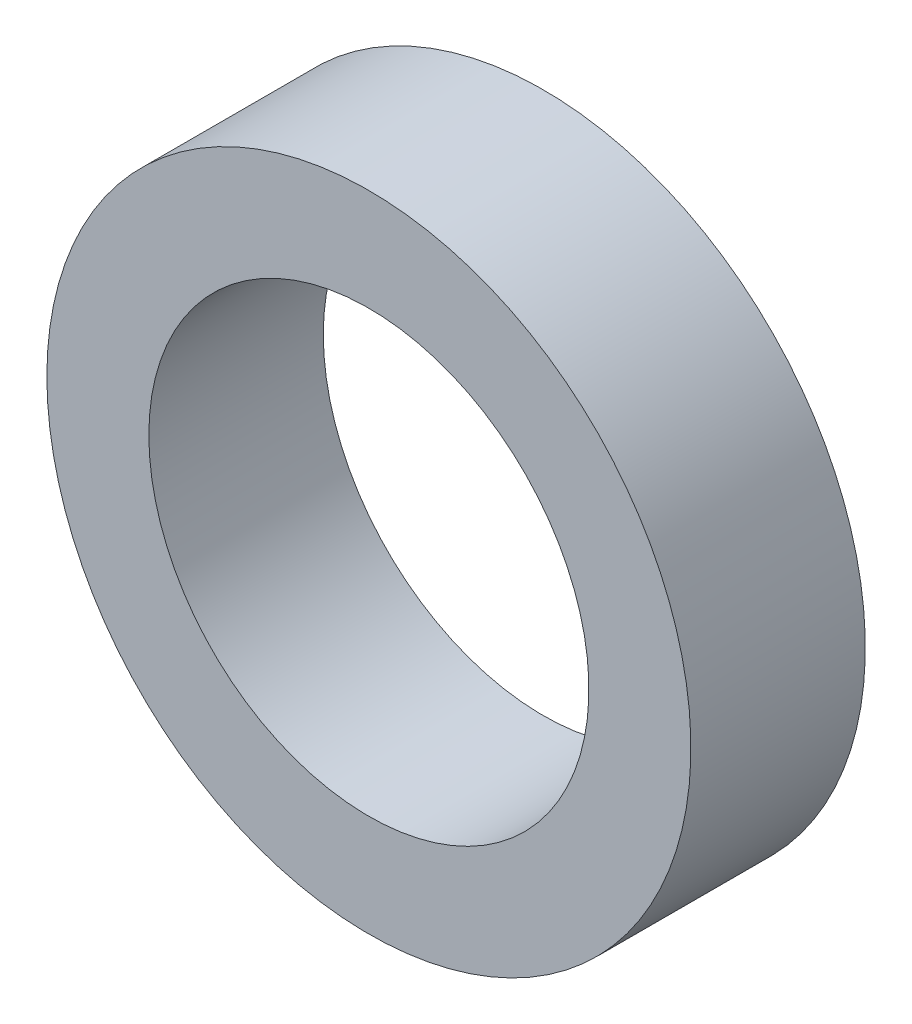
SolidWorks part; units mm, degrees
ref_plane "Front Plane" through (0, 0, 0) normal (0, 0, 1) x (1, 0, 0)
ref_plane "Top Plane" through (0, 0, 0) normal (0, 1, 0) x (1, 0, 0)
ref_plane "Right Plane" through (0, 0, 0) normal (1, 0, 0) x (0, 0, -1)
ref_axis "X" through (-88.99, 0, 0) along (1, 0, 0)
ref_axis "Y" through (0, 55, 0) along (0, -1, 0)
ref_axis "Z" through (0, 0, -88.99) along (0, 0, 1)
sketch "Sketch1" plane through (0, 0, 0) normal (0, 0, 1) x (1, 0, 0)
  circle A0 centre (0, 0) radius 4.1
  circle A1 centre (0, 0) radius 6
  dimension "D1" = 8.2
  dimension "D2" = 12
extrude "Boss-Extrude1" add sketch "Sketch1" along normal mid plane 3.25
